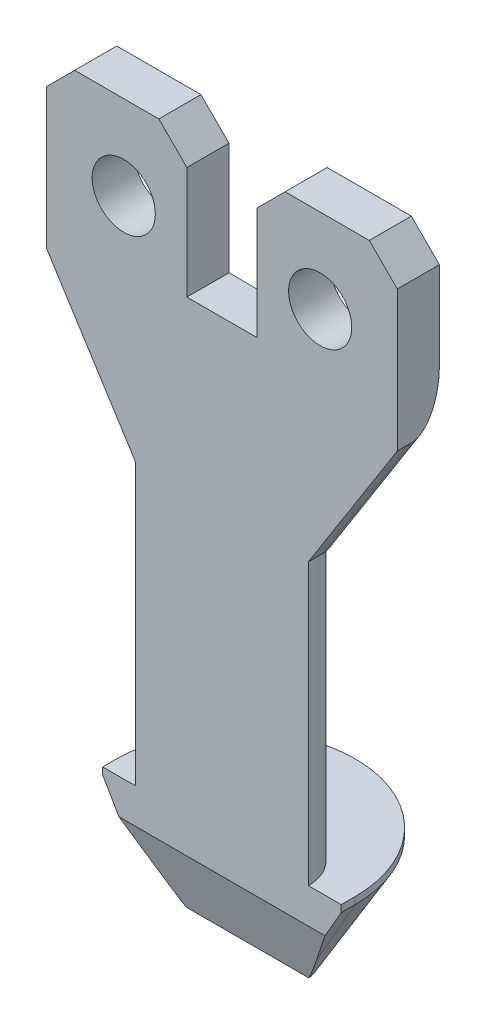
SolidWorks part; units mm, degrees
ref_plane "Front Plane" through (0, 0, 0) normal (0, 0, 1) x (1, 0, 0)
ref_plane "Top Plane" through (0, 0, 0) normal (0, 1, 0) x (1, 0, 0)
ref_plane "Right Plane" through (0, 0, 0) normal (1, 0, 0) x (0, 0, -1)
sketch "Sketch1" plane through (0, 0, 0) normal (0, 0, 1) x (1, 0, 0)
  line L0 (2.0184, -5.0594) -> (-2.9816, -5.0594)
  line L1 (-2.9816, -5.0594) -> (-2.9816, 4.9406)
  line L2 (-2.9816, 4.9406) -> (-12.9816, 4.9406)
  line L3 (-12.9816, 4.9406) -> (-12.9816, -7.0594)
  line L4 (-12.9816, -7.0594) -> (12.0184, -7.0594)
  line L5 (12.0184, -7.0594) -> (12.0184, 4.9406)
  line L6 (12.0184, 4.9406) -> (2.0184, 4.9406)
  line L7 (2.0184, 4.9406) -> (2.0184, -5.0594)
  circle A0 centre (6.5184, -1.0594) radius 2.25
  circle A1 centre (-7.4816, -1.0594) radius 2.25
extrude "Boss-Extrude1" add sketch "Sketch1" along normal blind 3
sketch "Sketch2" plane through (0, 0, 3) normal (0, 0, 1) x (1, 0, 0)
  line L0 (-12.9816, -7.0594) -> (-8.9816, -37.0594)
  line L1 (-8.9816, -37.0594) -> (8.0184, -37.0594)
  line L2 (8.0184, -37.0594) -> (12.0184, -7.0594)
  line L3 (-0.4816, -7.0594) -> (-0.4816, -37.0594) construction
  line L4 (-12.9816, -7.0594) -> (12.0184, -7.0594) construction
  line L5 (-12.9816, -7.0594) -> (12.0184, -7.0594)
  dimension "D1" = 30
  dimension "D2" = 17
extrude "Boss-Extrude2" add sketch "Sketch2" against normal through all
sketch "Sketch4" plane through (0, -37.0594, 0) normal (0, -1, 0) x (1, 0, 0)
  line L0 (-8.9816, 2) -> (-8.9816, 3)
  line L1 (-8.9816, 3) -> (8.0184, 3)
  line L2 (8.0184, 3) -> (8.0184, 2)
  line L3 (-8.9816, 3) -> (8.0184, 3) construction
  line L4 (-8.9816, 0) -> (-8.9816, 3) construction
  arc A0 (-8.9816, 2) -> (8.0184, 2) centre (-0.4816, 2) ccw
  dimension "D1" = 17
  dimension "D2" = 1
extrude "Boss-Extrude3" add sketch "Sketch4" along normal blind 7.5
chamfer "Chamfer1" distance 7 angle 30 3 edges at (-8.9816, -44.5594, 2.5) (8.0184, -44.5594, 2.5) (-0.4816, -44.5594, -6.5) first distance on face at (-8.9816, -40.8094, 2.5) first distance on face at (8.0184, -40.8094, 2.5) first distance on face at (-0.4816, -39.5594, -1.169)
sketch "Sketch5" plane through (0, 0, 0) normal (0, 0, -1) x (-1, 0, 0)
  line L0 (6.6482, -37.0594) -> (6.6482, -17.0594)
  line L1 (8.7429, -37.0594) -> (-7.7798, -37.0594) construction
  line L2 (6.6482, -17.0594) -> (11.6482, -17.0594)
  line L3 (12.9816, -7.0594) -> (8.9816, -37.0594) construction
  line L4 (6.6482, -37.0594) -> (8.9816, -37.0594)
  line L5 (11.6482, -17.0594) -> (8.9816, -37.0594)
  line L6 (0.4816, -37.0594) -> (0.4816, -29.7034) construction
  line L7 (8.7429, -37.0594) -> (-7.7798, -37.0594) construction
  line L8 (-10.6851, -17.0594) -> (-8.0184, -37.0594)
  line L9 (-5.6851, -37.0594) -> (-8.0184, -37.0594)
  line L10 (-5.6851, -17.0594) -> (-10.6851, -17.0594)
  line L11 (-5.6851, -37.0594) -> (-5.6851, -17.0594)
  dimension "D1" = 20
  dimension "D2" = 5
extrude "Cut-Extrude1" cut sketch "Sketch5" against normal through all
fillet "Fillet1" radius 3 2 edges at (5.6851, -27.0594, 0) (-6.6482, -27.0594, 0)
chamfer "Chamfer2" distance 2 angle 45 6 edges at (10.6851, -17.0594, 1.5) (-11.6482, -17.0594, 1.5) (12.0184, 4.9406, 1.5) (-12.9816, 4.9406, 1.5) (-2.9816, 4.9406, 1.5) (2.0184, 4.9406, 1.5) first distance on face at (7.5904, -17.0594, 1.3447) first distance on face at (-12.3149, -12.0594, 1.5) first distance on face at (7.0184, 4.9406, 1.5) first distance on face at (-7.9816, 4.9406, 1.5) first distance on face at (-2.9816, -0.0594, 1.5)
chamfer "Chamfer3" distance 5 angle 20 1 edges at (-0.4816, -44.5594, 3) first distance on face at (-0.4673, -15.5098, 3)
sketch "Sketch6" plane through (0, 0, 0) normal (0, 0, -1) x (-1, 0, 0)
  line L0 (-5.6851, -17.0594) -> (-12.0184, -7.0594)
  line L1 (-2.6851, -17.0594) -> (-8.6851, -17.0594) construction
  line L2 (12.9816, -7.0594) -> (6.6482, -17.0594)
  line L3 (-10.9928, -14.7517) -> (-12.0184, -7.0594) construction
  line L4 (12.9816, -7.0594) -> (11.9125, -15.077) construction
  line L5 (9.3201, -17.0594) -> (11.9125, -15.077) construction
  line L6 (9.3201, -17.0594) -> (3.6482, -17.0594) construction
  line L7 (-10.9928, -14.7517) -> (-8.6851, -17.0594) construction
  line L8 (-10.9928, -14.7517) -> (-12.0184, -7.0594)
  line L9 (12.9816, -7.0594) -> (11.9125, -15.077)
  line L10 (9.3201, -17.0594) -> (11.9125, -15.077)
  line L11 (9.3201, -17.0594) -> (6.6482, -17.0594)
  line L12 (-10.9928, -14.7517) -> (-8.6851, -17.0594)
  line L13 (-5.6851, -17.0594) -> (-8.6851, -17.0594)
extrude "Cut-Extrude2" cut sketch "Sketch6" against normal through all
fillet "Fillet2" radius 2 2 edges at (8.8518, -12.0594, 0) (-9.8149, -12.0594, 0)
